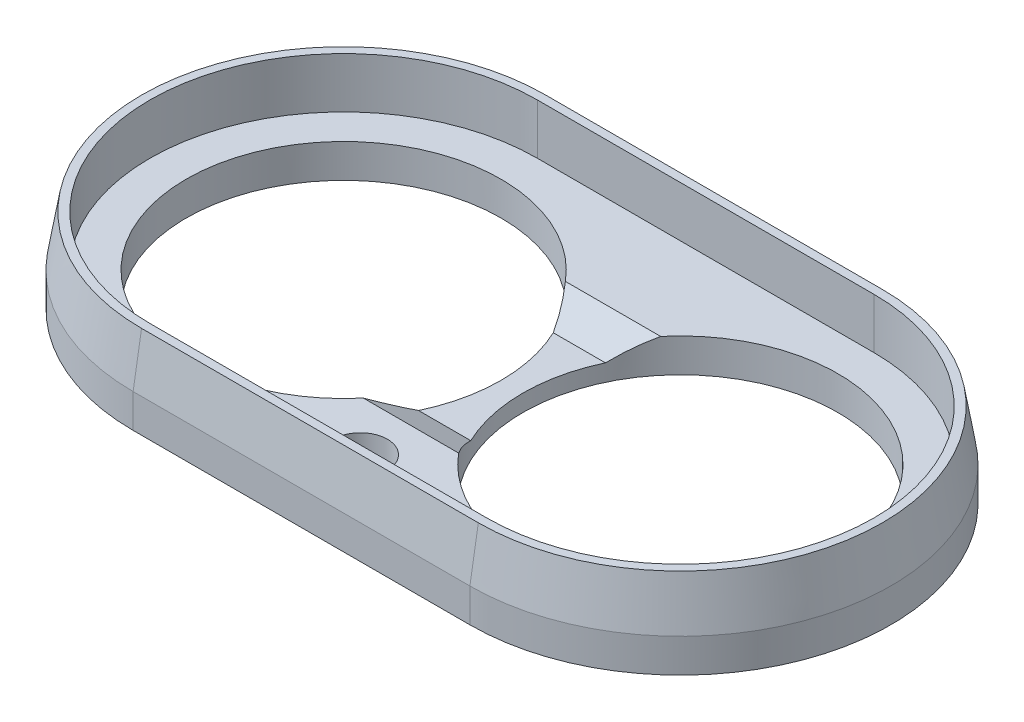
SolidWorks part; units mm, degrees
ref_plane "Front Plane" through (0, 0, 0) normal (0, 0, 1) x (1, 0, 0)
ref_plane "Top Plane" through (0, 0, 0) normal (0, 1, 0) x (1, 0, 0)
ref_plane "Right Plane" through (0, 0, 0) normal (1, 0, 0) x (0, 0, -1)
sketch "Sketch1" plane through (0, 0, 0) normal (0, 1, 0) x (1, 0, 0)
  line L0 (-10, 0) -> (10, 0)
  line L1 (10, 0) -> (22.5, 0)
  line L2 (10, 12.5) -> (-10, 12.5)
  line L3 (0, 12.5) -> (0, -12.5)
  line L4 (0, 19.9863) -> (0, -22.3991) construction
  line L5 (33.4627, 0) -> (-36.5916, 0) construction
  line L6 (-10, 0) -> (-22.5, 0)
  line L7 (10, -12.5) -> (-10, -12.5)
  arc A0 (10, -12.5) -> (10, 12.5) centre (10, 0) ccw
  arc A1 (-10, -12.5) -> (-10, 12.5) centre (-10, 0) cw
  point P16 (0, 0)
  dimension "D1" = 10
extrude "Boss-Extrude1" add sketch "Sketch1" along normal blind 2 contours A1 L6 L0 L3 L2 | A1 L7 L3 L0 L6 | L7 A0 L1 L0 L3 | L1 A0 L2 L3 L0 region at (-10.1051, 0, -5.7819) region at (-10.1051, 0, 5.7819) region at (10.1051, 0, -5.7819) region at (10.1051, 0, 5.7819)
sketch "Sketch2" plane through (0, 2, 0) normal (0, 1, 0) x (1, 0, 0)
  line L0 (0, 15.683) -> (0, -16.5594) construction
  circle A1 centre (10, 0) radius 9.35
  circle A2 centre (-10, 0) radius 9.35
  dimension "D1" = 18.7
  dimension "D2" = 10
extrude "Cut-Extrude1" cut sketch "Sketch2" against normal through all
sketch "Sketch3" plane through (0, 2, 0) normal (0, 1, 0) x (1, 0, 0)
  line L2 (10, 11.5) -> (-10, 11.5)
  line L3 (-10, -11.5) -> (10, -11.5)
  line L4 (-10, -12.5) -> (10, -12.5)
  line L5 (10, 12.5) -> (-10, 12.5)
  line L6 (-10, -12.5) -> (10, -12.5)
  line L7 (10, 12.5) -> (-10, 12.5)
  arc A2 (-10, 11.5) -> (-10, -11.5) centre (-10, 0) ccw
  arc A3 (10, -11.5) -> (10, 11.5) centre (10, 0) ccw
  arc A4 (10, -12.5) -> (10, 12.5) centre (10, 0) ccw
  arc A5 (-10, 12.5) -> (-10, -12.5) centre (-10, 0) ccw
  arc A6 (10, -12.5) -> (10, 12.5) centre (10, 0) ccw
  arc A7 (-10, 12.5) -> (-10, -12.5) centre (-10, 0) ccw
  dimension "D1" = 0
  dimension "D2" = 1
extrude "Boss-Extrude2" add sketch "Sketch3" along normal blind 3
chamfer "Chamfer1" distance 3 distance2 0.5 4 edges at (0, 5, -12.5) (22.5, 5, 0) (0, 5, 12.5) (-22.5, 5, 0) first distance on face at (0, 2.5, -12.5) first distance on face at (16.25, 2.5, 0) first distance on face at (0, 2.5, 12.5) first distance on face at (-16.25, 2.5, 0)
sketch "Sketch4" plane through (0, 2, 0) normal (0, 1, 0) x (1, 0, 0)
  line L1 (-7.5, -6) -> (7.5, -6)
  line L2 (-7.5, -6) -> (-7.5, 6)
  line L3 (-7.5, 6) -> (7.5, 6)
  line L4 (7.5, -6) -> (7.5, 6)
  line L5 (-7.5, -6) -> (7.5, 6) construction
  line L6 (-7.5, 6) -> (7.5, -6) construction
  point P0 (0, 0)
  dimension "D1" = 15
  dimension "D2" = 12
extrude "Cut-Extrude2" cut sketch "Sketch4" against normal blind 1
chamfer "Chamfer2" distance 1 distance2 2 2 edges at (0, 1, 6) (0, 1, -6) first distance on face at (0, 1.5, 6) first distance on face at (0, 1.5, -6)
sketch "Sketch5" plane through (0, 0, 0) normal (0, -1, 0) x (1, 0, 0)
  line L0 (10, 12.5) -> (-10, 12.5) construction
  circle A0 centre (0, 9) radius 1.6
  circle A1 centre (-4, 9.5) radius 0.75
  circle A2 centre (4, 9.5) radius 0.75
  dimension "D6" = 1.5
  dimension "D7" = 1.5
  dimension "D8" = 3.2
  dimension "D1" = 3.5
  dimension "D2" = 3
  dimension "D3" = 3
  dimension "D4" = 4
  dimension "D5" = 4
extrude "Cut-Extrude3" cut sketch "Sketch5" against normal through all
